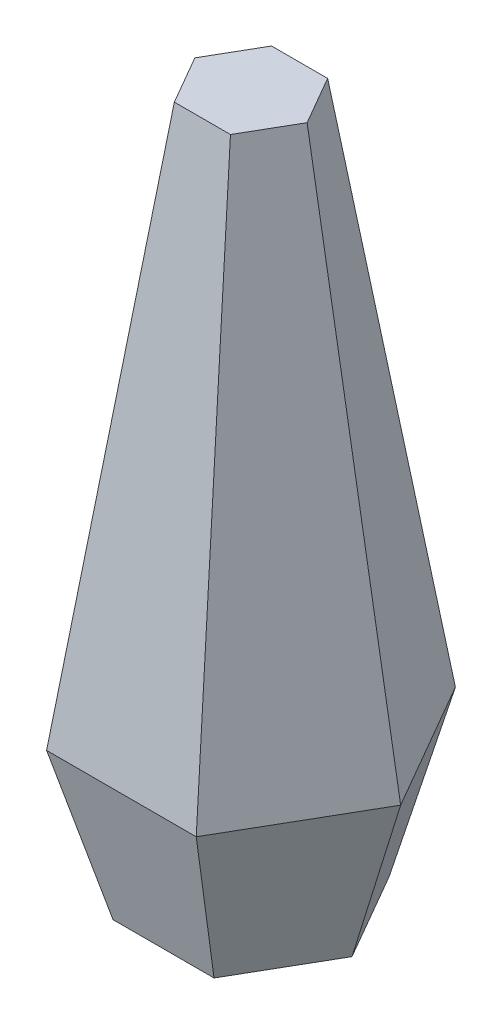
SolidWorks part; units mm, degrees
ref_plane "Front Plane" through (0, 0, 0) normal (0, 0, 1) x (1, 0, 0)
ref_plane "Top Plane" through (0, 0, 0) normal (0, 1, 0) x (1, 0, 0)
ref_plane "Right Plane" through (0, 0, 0) normal (1, 0, 0) x (0, 0, -1)
ref_plane "Plane1" through (0, 609.6, 0) normal (0, 1, 0) x (-1, 0, 0)
sketch "Sketch1" plane through (0, 0, 0) normal (0, 1, 0) x (1, 0, 0)
  line L1 (395.9468, 0) -> (197.9734, 342.9)
  line L2 (197.9734, 342.9) -> (-197.9734, 342.9)
  line L3 (-197.9734, 342.9) -> (-395.9468, 0)
  line L4 (-395.9468, 0) -> (-197.9734, -342.9)
  line L5 (-197.9734, -342.9) -> (197.9734, -342.9)
  line L6 (197.9734, -342.9) -> (395.9468, 0)
  circle A0 centre (0, 0) radius 342.9 construction
sketch "Sketch3" plane through (0, 609.6, 0) normal (0, 1, 0) x (-1, 0, 0)
  line L1 (-586.5879, 0) -> (-293.2939, -508)
  line L2 (-293.2939, -508) -> (293.2939, -508)
  line L3 (293.2939, -508) -> (586.5879, 0)
  line L4 (586.5879, 0) -> (293.2939, 508)
  line L5 (293.2939, 508) -> (-293.2939, 508)
  line L6 (-293.2939, 508) -> (-586.5879, 0)
  circle A0 centre (0, 0) radius 508 construction
ref_plane "Plane2" through (0, 2743.2, 0) normal (0, 1, 0) x (-1, 0, 0)
sketch "Sketch4" plane through (0, 2743.2, 0) normal (0, 1, 0) x (-1, 0, 0)
  line L1 (219.9705, 0) -> (109.9852, 190.5)
  line L2 (109.9852, 190.5) -> (-109.9852, 190.5)
  line L3 (-109.9852, 190.5) -> (-219.9705, 0)
  line L4 (-219.9705, 0) -> (-109.9852, -190.5)
  line L5 (-109.9852, -190.5) -> (109.9852, -190.5)
  line L6 (109.9852, -190.5) -> (219.9705, 0)
  circle A0 centre (0, 0) radius 190.5 construction
loft "Loft6" add profiles "Sketch1", "Sketch3" start constraint default connector at (197.9734, 0, -342.9) connector at (293.2939, 609.6, -508)
loft "Loft7" add profiles "Sketch3<4>", "Sketch4"
sketch "Sketch3<4>" plane through (0, 609.6, 0) normal (0, 1, 0) x (-1, 0, 0) same geometry as "Sketch3"
